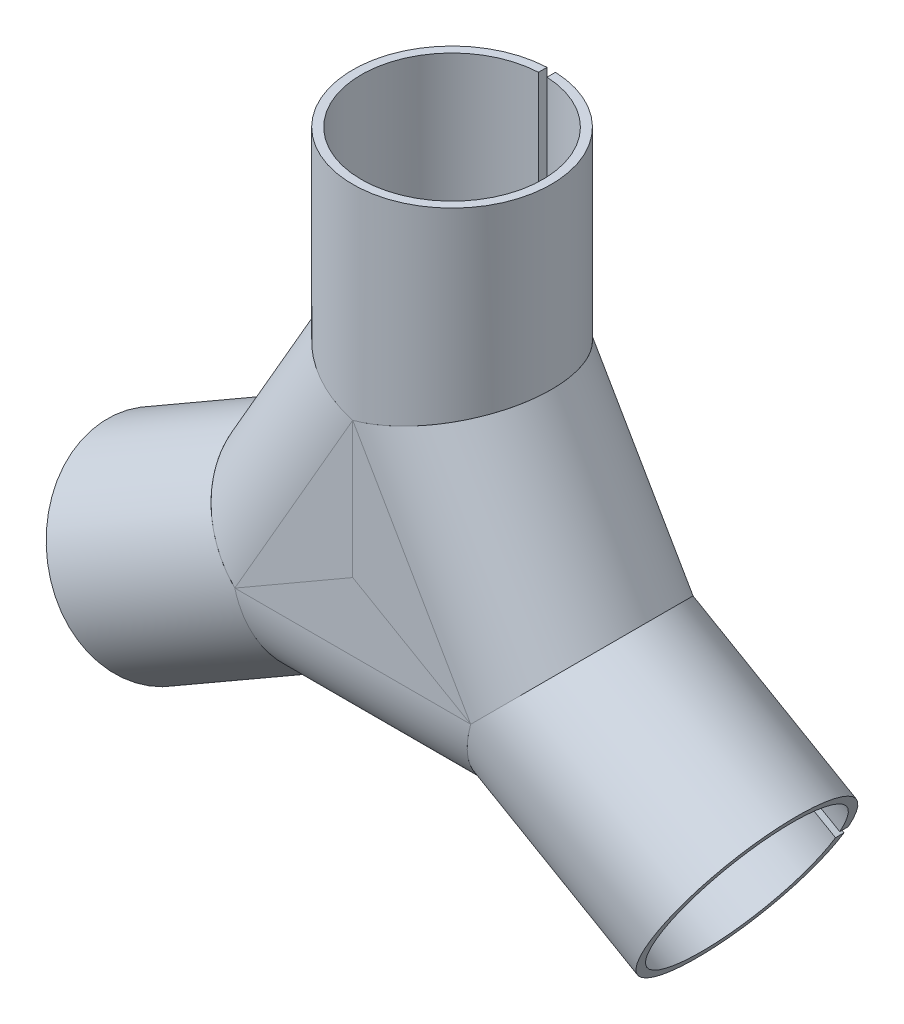
SolidWorks part; units mm, degrees
ref_plane "前视基准面" through (0, 0, 0) normal (0, 0, 1) x (1, 0, 0)
ref_plane "上视基准面" through (0, 0, 0) normal (0, 1, 0) x (1, 0, 0)
ref_plane "右视基准面" through (0, 0, 0) normal (1, 0, 0) x (0, 0, -1)
sketch "草图1" plane through (0, 0, 0) normal (0, 0, 1) x (1, 0, 0)
  line L0 (0, 40) -> (0, 0) construction
  line L1 (0, 0) -> (-34.641, -20) construction
  line L2 (0, 0) -> (34.641, -20) construction
  line L3 (-11.6658, 40) -> (11.6658, 40) construction
  line L4 (-11.6658, 40) -> (-11.6658, 19.1258) construction
  line L5 (-11.6658, 19.1258) -> (-22.3964, 0.54) construction
  line L6 (-22.3964, 0.54) -> (-40.4739, -9.8971) construction
  line L7 (-40.4739, -9.8971) -> (-28.8081, -30.1029) construction
  line L8 (-28.8081, -30.1029) -> (-10.7306, -19.6658) construction
  line L9 (-10.7306, -19.6658) -> (10.7306, -19.6658) construction
  line L10 (10.7306, -19.6658) -> (28.8081, -30.1029) construction
  line L11 (28.8081, -30.1029) -> (40.4739, -9.8971) construction
  line L12 (40.4739, -9.8971) -> (22.3964, 0.54) construction
  line L13 (22.3964, 0.54) -> (11.6658, 19.1258) construction
  line L14 (11.6658, 19.1258) -> (11.6658, 40) construction
  line L15 (0, 0) -> (0, -19.6658) construction
  line L16 (0, -19.6658) -> (0, -20.6658) construction
  line L17 (-22.3964, 0.54) -> (-13.8564, -8) construction
  line L18 (-13.8564, -8) -> (-10.7306, -19.6658) construction
  line L19 (10.7306, -19.6658) -> (13.8564, -8) construction
  line L20 (13.8564, -8) -> (22.3964, 0.54) construction
  line L21 (-11.6658, 19.1258) -> (0, 16) construction
  line L22 (0, 16) -> (11.6658, 19.1258) construction
  line L23 (-13.8564, -8) -> (0, 16) construction
  line L24 (-6.9282, 4) -> (-17.0311, 9.8329) construction
  line L25 (0, 40) -> (11.6658, 40) construction
  line L26 (-13.8564, -8) -> (13.8564, -8) construction
  line L27 (0, 0) -> (0, 40)
  dimension "D1" = 120
  dimension "R" = 11.6658
  dimension "L1" = 40
  dimension "t" = 1
  dimension "L2" = 16
sketch "草图2" plane through (0, 0, 0) normal (0, 1, 0) x (1, 0, 0)
  line L0 (0, 11.6658) -> (0, -11.6658) construction
  circle A0 centre (0, 0) radius 11.6658
ref_plane "基准面1" through (-6.9282, 4, 0) normal (0.5, 0.866, 0) x (-0.866, 0.5, 0)
sketch "草图3" plane through (-6.9282, 4, 0) normal (0.5, 0.866, 0) x (-0.866, 0.5, 0)
  circle A0 centre (0, 0) radius 11.6658
extrude "拉伸-薄壁1" add sketch "草图2" along normal up to vertex (40 mm away) thin up to point (0, 40, 0) thin type one direction reverse wall 1
extrude "拉伸-薄壁2" add sketch "草图3" along normal up to vertex (13.8564 mm away) and the other way up to vertex (13.8564 mm away) separate body thin up to point (0, 16, 0) other way up to point (-13.8564, -8, 0) thin type one direction reverse wall 1
sketch "草图4" plane through (0, 0, 0) normal (0, 0, 1) x (1, 0, 0)
  line L0 (-11.6658, 40) -> (-11.6658, 19.1258) construction
  line L1 (11.6658, 19.1258) -> (11.6658, 40) construction
  line L2 (-11.6658, 40) -> (11.6658, 40) construction
  line L3 (0, 16) -> (11.6658, 19.1258) construction
  line L4 (-11.6658, 19.1258) -> (0, 16) construction
  line L5 (-11.6658, 40) -> (-11.6658, 19.1258)
  line L6 (11.6658, 19.1258) -> (11.6658, 40)
  line L7 (-11.6658, 40) -> (11.6658, 40)
  line L8 (0, 16) -> (11.6658, 19.1258)
  line L9 (-11.6658, 19.1258) -> (0, 16)
extrude "切除-拉伸1" cut sketch "草图4" against normal through all and the other way through all flip side to cut
sketch "草图5" plane through (0, 0, 0) normal (0, 0, 1) x (1, 0, 0)
  line L1 (-11.6658, 19.1258) -> (0, 16) construction
  line L2 (-11.6658, 19.1258) -> (-22.3964, 0.54) construction
  line L3 (-22.3964, 0.54) -> (-13.8564, -8) construction
  line L4 (-11.6658, 19.1258) -> (0, 16)
  line L5 (-11.6658, 19.1258) -> (-22.3964, 0.54)
  line L6 (-22.3964, 0.54) -> (-13.8564, -8)
  line L7 (-13.8564, -8) -> (0, 16) construction
  line L8 (-13.8564, -8) -> (0, 16)
extrude "切除-拉伸2" cut sketch "草图5" against normal through all and the other way through all flip side to cut
ref_plane "基准面2" through (0, 0, 11.6658) normal (0, 0, 1) x (1, 0, 0)
sketch "草图7" plane through (0, 0, 11.6658) normal (0, 0, 1) x (1, 0, 0)
  line L0 (0, 16) -> (0, 0)
  line L1 (0, 0) -> (-13.8564, -8)
  line L2 (-13.8564, -8) -> (0, 16) construction
  line L3 (-13.8564, -8) -> (0, 16)
extrude "凸台-拉伸1" add sketch "草图7" against normal blind 1
mirror "镜向1" about plane through (0, 0, 0) normal (0, 0, 1) of "凸台-拉伸1"
extrude "切除-拉伸-薄壁2" cut sketch "草图1" against normal through all thin thin type mid plane wall 1
ref_axis "基准轴1" through (0, 0, -12.8324) along (0, 0, 1)
pattern_circular "阵列(圆周)1" count 3 over 360 about axis through (0, 0, -12.8324) along (0, 0, 1) of bodies 115 116 104 105
equation "\"D5@拉伸-薄壁1\" = \"t@草图1\""
equation "\"D5@拉伸-薄壁2\" = \"t@草图1\""
equation "\"D1@凸台-拉伸1\" = \"t@草图1\""
